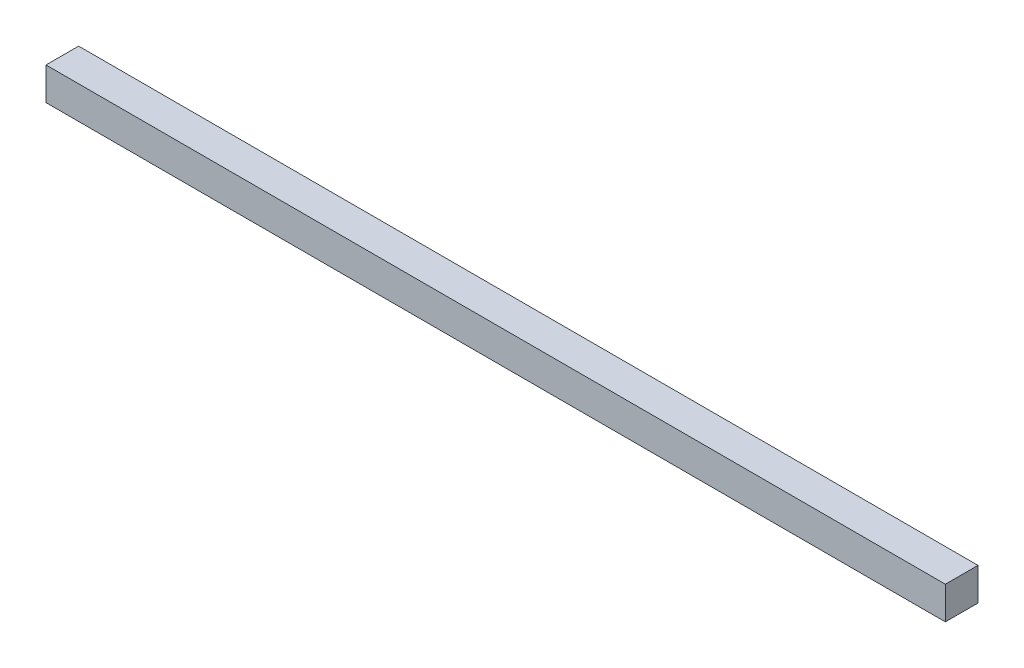
SolidWorks part; units mm, degrees
ref_plane "Front Plane" through (0, 0, 0) normal (0, 0, 1) x (1, 0, 0)
ref_plane "Top Plane" through (0, 0, 0) normal (0, 1, 0) x (1, 0, 0)
ref_plane "Right Plane" through (0, 0, 0) normal (1, 0, 0) x (0, 0, -1)
sketch "Sketch1" plane through (0, 0, 0) normal (0, 0, 1) x (1, 0, 0)
  line L0 (-124, 0) -> (124, 0) construction
  line L1 (0, -22.3452) -> (0, 22.3452) construction
  dimension "D1" = 248
sketch "Sketch2" plane through (0, 0, 0) normal (1, 0, 0) x (0, 0, -1)
  line L1 (-4.5, -4.5) -> (4.5, -4.5)
  line L2 (-4.5, -4.5) -> (-4.5, 4.5)
  line L3 (-4.5, 4.5) -> (4.5, 4.5)
  line L4 (4.5, -4.5) -> (4.5, 4.5)
  line L5 (-4.5, -4.5) -> (4.5, 4.5) construction
  line L6 (-4.5, 4.5) -> (4.5, -4.5) construction
  point P0 (0, 0)
  dimension "D1" = 9
extrude "Boss-Extrude1" add sketch "Sketch2" against normal up to vertex (124 mm away) and the other way up to vertex (124 mm away) up to point (-124, 0, 0) other way up to point (124, 0, 0)
